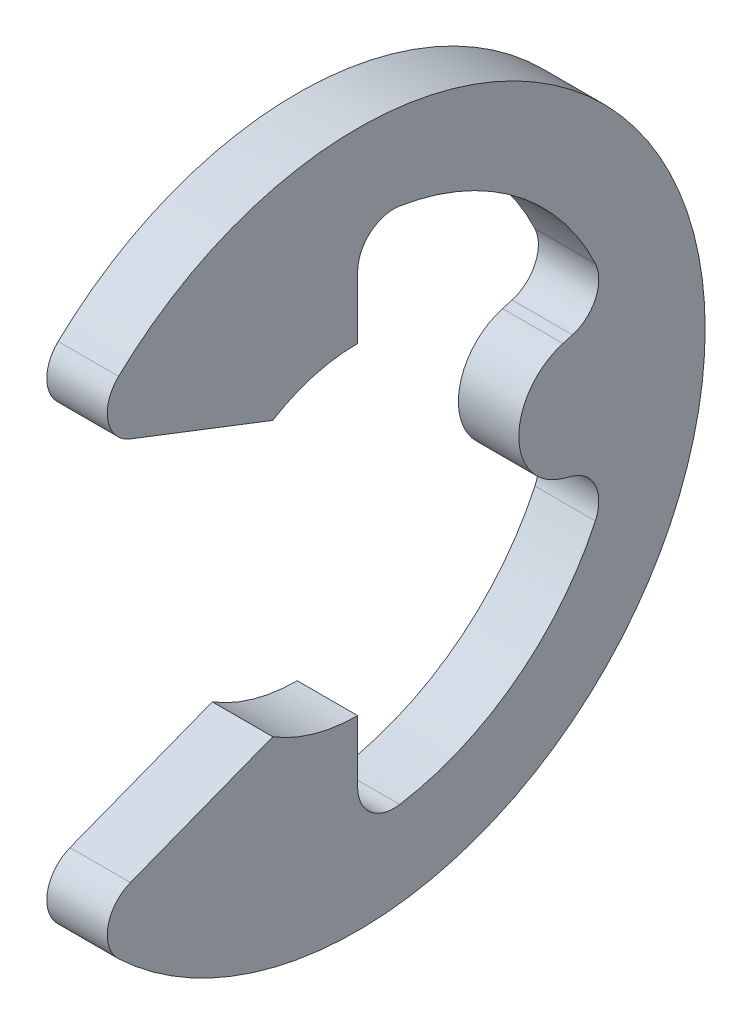
SolidWorks part; units mm, degrees
note: '?' marks a value the reader was unsure of.
other "Imported1" parameters "D1"=0.36, "D2"=1.7342, "Ring Thickness"=0.6, "Groove Width"=0.64, "OD"=95.4673, "L2"=3.25, "Df"=44.9367, "Dg"=1.2, "D5"=1.1938, "G"=2.9, "D3"=8.0325, "D4"=4.6385, "A"=1.01, "Ring OD"=19.0132, "Groove Diameter"=9.0385
ref_plane "Front" through (0, 0, 0) normal (0, 0, 1) x (1, 0, 0)
ref_plane "Top" through (0, 0, 0) normal (0, 1, 0) x (1, 0, 0)
ref_plane "Right" through (0, 0, 0) normal (1, 0, 0) x (0, 0, -1)
sketch "Sketch2" plane through (0, 0, 0) normal (1, 0, 0) x (0, 0, -1)
  circle A0 centre (0, 0) radius 3.45 construction
  circle A1 centre (0, 0) radius 1.6 construction
  dimension "Ring OD" = 6.9
sketch "Sketch3" plane through (0, 0, 0) normal (0, 1, 0) x (1, 0, 0)
  line L0 (0.3, 3.45) -> (-0.3, 3.45) construction
  line L1 (-0.32, -2.415) -> (0.32, -2.415) construction
  line L3 (0, -3.45) -> (0, 3.45) construction
  line L4 (0, -3.45) -> (0, 3.45) construction
  point P4 (0, -2.415)
  point P6 (0, 3.45)
  dimension "D1" = 2.07
sketch "Sketch1" plane through (0, 0, 0) normal (1, 0, 0) x (0, 0, -1)
  line L0 (-2.7412, -2.0948) -> (-0.8429, -1.36)
  line L1 (-2.7412, 2.0948) -> (-0.8429, 1.36)
  line L2 (0, -1.6) -> (0, -2.6065)
  line L3 (0, 1.6) -> (0, 2.6065)
  line L4 (1.5388, -0.4382) -> (2.5068, -0.7138)
  line L5 (1.5388, 0.4382) -> (2.5068, 0.7138)
  line L6 (0, 0) -> (-1.625, 0) construction
  line L7 (1.5388, 0.4382) -> (1.5388, -0.4382) construction
  line L8 (-0.8429, 1.36) -> (0, 1.6) construction
  line L9 (-0.8429, -1.36) -> (0, -1.6) construction
  circle A1 centre (0, 0) radius 3.45 construction
  circle A2 centre (0, 0) radius 1.6 construction
  arc A3 (-2.7412, -2.0948) -> (-2.7412, 2.0948) centre (0, 0) ccw
  arc A4 (-0.8429, 1.36) -> (0, 1.6) centre (0, 0) cw
  arc A5 (-0.8429, -1.36) -> (0, -1.6) centre (0, 0) ccw
  arc A6 (1.5388, 0.4382) -> (1.5388, -0.4382) centre (0, 0) cw
  arc A7 (0, -2.6065) -> (2.5068, -0.7138) centre (0, 0) ccw
  arc A8 (2.5068, 0.7138) -> (0, 2.6065) centre (0, 0) ccw
  circle A9 centre (0, 0) radius 1.6 construction
  point P12 (1.5388, 0)
  dimension "D1" = 2.6065
  dimension "D2" = 1.9282
  dimension "D3" = 2.72
extrude "Extrude1" add sketch "Sketch1" along normal mid plane 0.6
fillet "Fillet1" radius 0.36 6 edges at (0, -2.6065, 0) (0, 2.6065, 0) (0, -2.0948, 2.7412) (0, 2.0948, 2.7412) (0, -0.7138, -2.5068) (0, 0.7138, -2.5068)
sketch "Sketch4" plane through (0, 0, 0) normal (1, 0, 0) x (0, 0, -1)
  line L0 (-3.45, 0) -> (3.45, 0) construction
  line L5 (2.1326, 0.6073) -> (1.5388, 0.4382) construction
  line L6 (1.5388, -0.4382) -> (2.1326, -0.6073) construction
  line L7 (1.5388, -0.4382) -> (2.0382, -0.5804)
  line L8 (2.0382, 0.5804) -> (1.5388, 0.4382)
  arc A4 (2.0382, 0.5804) -> (2.0382, -0.5804) centre (2.2034, 0) ccw
  circle A5 centre (0, 0) radius 1.6 construction
  arc A6 (1.5388, -0.4382) -> (1.5388, 0.4382) centre (0, 0) ccw
extrude "Cut-Extrude1" cut sketch "Sketch4" against normal through all both and the other way through all contours A6 A4 L8 | A6 L7 A4
ref_plane "Contact Plane 1" through (0.3, 0, 0) normal (1, 0, 0) x (0, 0, -1)
ref_plane "Contact Plane 2" through (-0.3, 0, 0) normal (-1, 0, 0) x (0, 0, 1)
ref_axis "Center Axis 1" through (5.5343, 0, 0) along (-1, 0, 0)?
equation "\"D1@Fillet1\" = \"Ring Thickness@Sketch3\" * .6"
equation "\"D1@Sketch1\" = ( \"Ring OD@Sketch2\" + \"Groove Diameter@Sketch2\" ) / 3.875"
equation "\"D1@Sketch3\"=\"Ring OD@Sketch2\"*.3"
equation "\"D3@Sketch1\"=\"Groove Diameter@Sketch2\"*.85"
